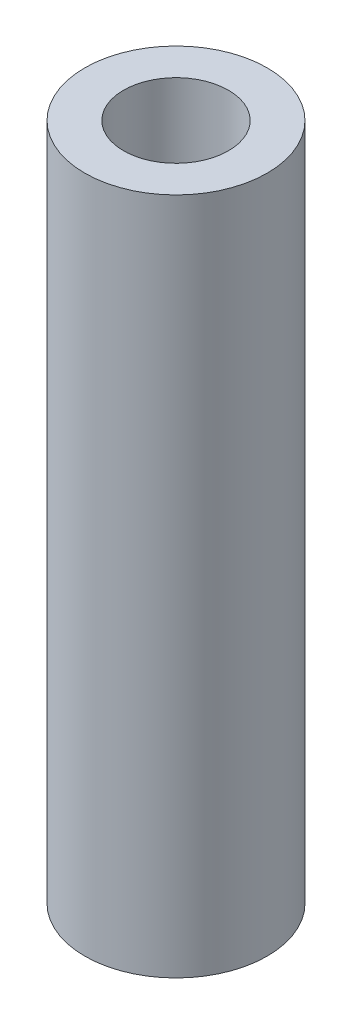
SolidWorks part; units mm, degrees
ref_plane "Front Plane" through (0, 0, 0) normal (0, 0, 1) x (1, 0, 0)
ref_plane "Top Plane" through (0, 0, 0) normal (0, 1, 0) x (1, 0, 0)
ref_plane "Right Plane" through (0, 0, 0) normal (1, 0, 0) x (0, 0, -1)
sketch "Sketch1" plane through (0, 0, 0) normal (0, 1, 0) x (1, 0, 0)
  circle A0 centre (0, 0) radius 5.65
  circle A1 centre (0, 0) radius 3.25
  dimension "D1" = 6.5
  dimension "D2" = 2.4
extrude "Boss-Extrude1" add sketch "Sketch1" along normal blind 42
